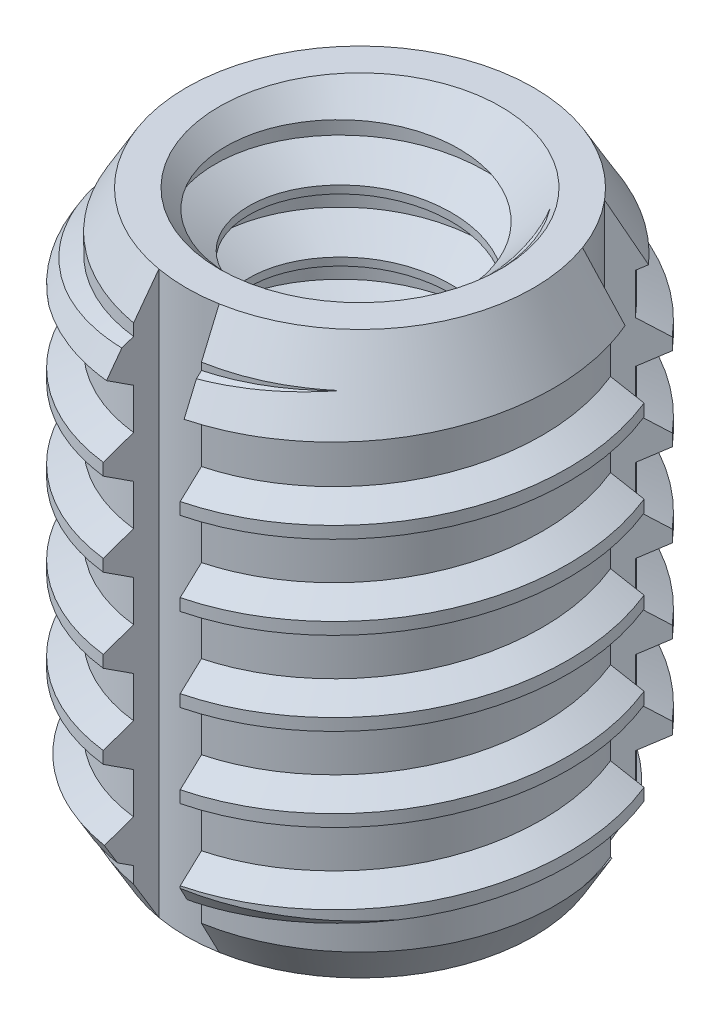
SolidWorks part; units mm, degrees
note: '?' marks a value the reader was unsure of.
ref_plane "Front Plane" through (0, 0, 0) normal (0, 0, 1) x (1, 0, 0)
ref_plane "Top Plane" through (0, 0, 0) normal (0, 1, 0) x (1, 0, 0)
ref_plane "Right Plane" through (0, 0, 0) normal (1, 0, 0) x (0, 0, -1)
sketch "Sketch1" plane through (0, 0, 0) normal (0, 1, 0) x (1, 0, 0)
  line L0 (-3.7592, 0) -> (3.7592, 0) construction
  circle A0 centre (0, 0) radius 3.7592
  dimension "External Thread OD" = 7.5184
extrude "Extrude1" add sketch "Sketch1" against normal blind 9.525
sketch "Sketch2" plane through (0, 0, 0) normal (0, 1, 0) x (1, 0, 0)
  circle A2 centre (0, 0) radius 2.413
  point P0 (-2.413, 0)
  dimension "Internal Thread OD" = 4.826
curve "Helix/Spiral1" pitch 1.0583 height 10.5833 turns 10 parameters "Internal Thread Height"=10.5833, "Internal Thread Pitch"=1.0583
sketch "Sketch3" plane through (0, 0, 0) normal (0, 0, 1) x (1, 0, 0)
  line L0 (-1.611, 0.9922) -> (-1.611, -0.0661) construction
  line L1 (-1.611, -0.0661) -> (-2.5276, 0.463) construction
  line L2 (-2.5276, 0.463) -> (-1.611, 0.9922) construction
  line L3 (-1.611, 0.463) -> (-1.7256, 0.463) construction
  line L4 (-1.7256, 0.463) -> (-2.2984, 0.463) construction
  line L5 (-2.413, 0.463) -> (-2.5276, 0.463) construction
  line L6 (-2.413, 0.5292) -> (-2.413, 0.3969) construction
  line L7 (-1.7256, 0) -> (-1.7256, 0.926) construction
  line L8 (-2.413, 0.3969) -> (-2.413, 0) construction
  line L9 (-2.413, 0) -> (-1.7256, 0) construction
  line L10 (-2.2984, 0.5953) -> (-2.2984, 0.3307)
  line L11 (-2.2984, 0.3307) -> (-1.6683, -0.0331)
  line L12 (-1.6683, -0.0331) -> (-1.6683, 0.9591)
  line L13 (-1.6683, 0.9591) -> (-2.2984, 0.5953)
  line L14 (-2.413, 0.463) -> (-2.2984, 0.463) construction
  point P18 (-1.6683, 0.463)
  dimension "D1" = 1.0583
  dimension "D2" = 0.1323
sketch "Sketch4" plane through (0, 0, 0) normal (0, 1, 0) x (-1, 0, 0)
  circle A0 centre (0, 0) radius 1.7256
extrude "Extrude2" cut sketch "Sketch4" against normal through all
chamfer "Chamfer1" distance 0.6615 angle 45 2 edges at (0, 0, 1.7256) (0, -9.525, 1.7256)
sweep "Cut-Sweep1" cut profiles "Sketch3" path "Helix/Spiral1"
sketch "Sketch5" plane through (0, 0, 0) normal (0, 1, 0) x (1, 0, 0)
  circle A0 centre (0, 0) radius 3.7592 construction
  circle A1 centre (0, 0) radius 3.7592
  point P3 (-3.7592, 0)
curve "Helix/Spiral2" pitch 1.4111 height 10.5833 turns 7.5 parameters "External Thread Height"=10.5833, "External Thread Pitch"=1.4111
sketch "Sketch6" plane through (0, 0, 0) normal (0, 0, 1) x (1, 0, 0)
  line L0 (-3.9356, 1.3093) -> (-3.9356, -0.1018) construction
  line L1 (-3.9356, 1.3093) -> (-2.7135, 0.6037) construction
  line L2 (-2.7135, 0.6037) -> (-3.9356, -0.1018) construction
  line L3 (-3.7592, 1.2074) -> (-3.7592, 0) construction
  line L4 (-3.3147, 0.9508) -> (-3.3147, 0.2566)
  line L5 (-3.8474, 1.2584) -> (-3.3147, 0.9508)
  line L6 (-3.8474, 1.2584) -> (-3.8474, -0.0509)
  line L7 (-3.8474, -0.0509) -> (-3.3147, 0.2566)
  line L8 (-3.9356, 0.6037) -> (-3.7592, 0.6037) construction
  line L9 (-3.3147, 0.6037) -> (-2.7135, 0.6037) construction
  line L10 (0, 0) -> (0, 1.2074) construction
  point P13 (-3.8474, 0.6037)
  dimension "D1" = 1.4111
  dimension "D3" = 0.1764
chamfer "Chamfer2" distance 1.4111 angle 30 1 edges at (0, 0, 3.7592)
chamfer "Chamfer3" distance 1.4111 angle 30 1 edges at (0, -9.525, 3.7592)
sweep "Cut-Sweep2" cut profiles "Sketch6" path "Helix/Spiral2"
sketch "Sketch7" plane through (0, 0, 0) normal (0, 1, 0) x (1, 0, 0)
  line L0 (0, 0) -> (0, -2.9445) construction
  line L1 (0, -2.9445) -> (0, -3.7592) construction
  line L2 (-0.5113, -2.8998) -> (-0.6528, -3.7021)
  line L3 (0.5113, -2.8998) -> (0.6528, -3.7021)
  circle A0 centre (0, 0) radius 3.7592 construction
  arc A2 (-0.6528, -3.7021) -> (0.6528, -3.7021) centre (0, 0) ccw
  circle A3 centre (0, 0) radius 2.9445 construction
  arc A4 (-0.5113, -2.8998) -> (0.5113, -2.8998) centre (0, 0) ccw
  dimension "D1" = 20
extrude "Extrude3" cut sketch "Sketch7" against normal through all
ref_axis "Axis1" through (0, 0.6691, 0) along (0, -1, 0)?
pattern_circular "CirPattern1" count 3 over 360 about axis through (0, 0, 0) along (0, 1, 0) of "Extrude3"
equation "\"Internal Thread Height@Helix/Spiral1\" = \"Internal Thread Pitch@Helix/Spiral1\" + \"Length@Extrude1\""
equation "\"D1@Sketch3\" = \"Internal Thread Pitch@Helix/Spiral1\""
equation "\"D2@Sketch3\" = \"D1@Sketch3\" / 8"
equation "\"D1@Chamfer1\" = \"Internal Thread Pitch@Helix/Spiral1\" * 5 / 8"
equation "\"External Thread Height@Helix/Spiral2\" = \"Internal Thread Height@Helix/Spiral1\""
equation "\"D1@Sketch6\" = \"External Thread Pitch@Helix/Spiral2\""
equation "\"D1@Chamfer2\" = \"External Thread Pitch@Helix/Spiral2\" * 8 / 8"
equation "\"D3@Sketch6\" = \"D1@Sketch6\" * 1 / 8"
equation "\"D1@Chamfer3\" = \"D1@Chamfer2\""
